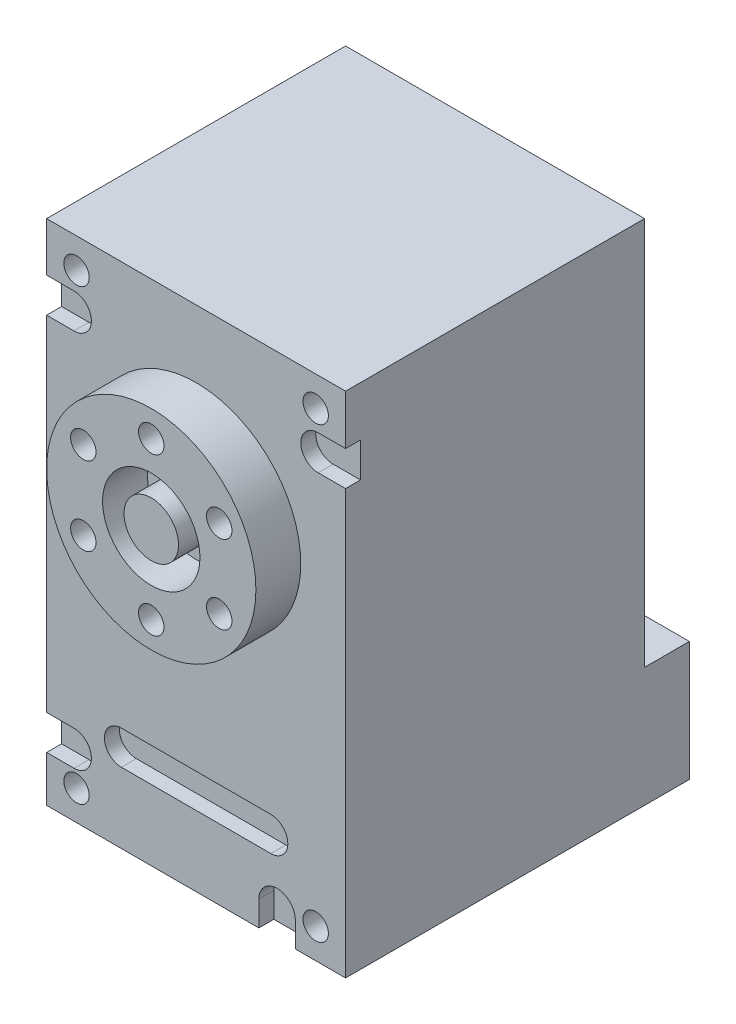
SolidWorks part; units mm, degrees
ref_plane "前视基准面" through (0, 0, 0) normal (0, 0, 1) x (1, 0, 0)
ref_plane "上视基准面" through (0, 0, 0) normal (0, 1, 0) x (1, 0, 0)
ref_plane "右视基准面" through (0, 0, 0) normal (1, 0, 0) x (0, 0, -1)
other "Configuration Table"
sketch "草图1" plane through (0, 0, 0) normal (0, 0, 1) x (1, 0, 0)
  line L0 (0, 0) -> (20, 0)
  line L1 (20, 0) -> (20, 34)
  line L2 (20, 34) -> (0, 34)
  line L3 (0, 34) -> (0, 0)
  line L4 (10, 0) -> (10, 34) construction
  line L5 (0, 17) -> (20, 17) construction
  circle A0 centre (2, 32) radius 0.85
  circle A1 centre (18, 32) radius 0.85
  circle A2 centre (18, 2) radius 0.85
  circle A3 centre (2, 2) radius 0.85
  circle A4 centre (10, 22.5) radius 7
  circle A5 centre (10, 27.75) radius 0.8504
  circle A6 centre (14.5466, 25.125) radius 0.8504
  circle A7 centre (14.5466, 19.875) radius 0.8504
  circle A8 centre (10, 17.25) radius 0.8504
  circle A9 centre (5.4534, 19.875) radius 0.8504
  circle A10 centre (5.4534, 25.125) radius 0.8504
  circle A11 centre (10, 22.5) radius 5.25
  circle A12 centre (10, 22.5) radius 3.2575
  circle A13 centre (10, 22.5) radius 1.8232
  point P34 (10, 22.5)
  dimension "D3" = 1.7
  dimension "D7" = 6
  dimension "D8" = 14
  dimension "D9" = 10.5
  dimension "D1" = 20
  dimension "D2" = 34
  dimension "D4" = 16
  dimension "D5" = 30
  dimension "D6" = 9.5
extrude "凸台-拉伸4" add sketch "草图1" along normal blind 3 contours A4 A11 A6 A7 A8 A9 A10 A5 | A6 A11 A5 A10 A9 A8 A7 A12 | A13 region at (3.198, 22.5, 0) region at (10, 26.7521, 0) region at (10, 22.5, 0)
sketch "草图3" plane through (0, 0, 3) normal (0, 0, 1) x (1, 0, 0)
extrude "凸台-拉伸5" add sketch "草图1<9>" against normal blind 20 contours A11 A7 | A7 A11 | A11 A5 | A11 A10 | A10 A11 | A11 A9 | A9 A11 | A11 A8 | A8 A11 | A6 A11 A5 A10 A9 A8 A7 A12 | A12 A13 | A13 | A1 | A0 | A2 | A3 | L2 L3 L0 L1 A4 A1 A0 A2 A3 | A4 A11 A6 A7 A8 A9 A10 A5 | A5 A11 | A6 region at (10, 15.3623, 0) region at (2, 32, 0) region at (18, 32, 0) region at (18, 2, 0) region at (2, 2, 0) region at (3.198, 22.5, 0) region at (10, 28.0982, 0) region at (10, 27.377, 0) region at (10, 26.7521, 0) region at (5.1518, 25.2991, 0) region at (5.7764, 24.9385, 0) region at (5.1518, 19.7009, 0) region at (5.7764, 20.0615, 0) region at (14.2236, 20.0615, 0) region at (14.8482, 19.7009, 0) region at (10, 16.9018, 0) region at (10, 17.623, 0) region at (6.8346, 22.5, 0) region at (10, 22.5, 0)
sketch "草图1<9>" plane through (0, 0, 0) normal (0, 0, 1) x (1, 0, 0) same geometry as "草图1"
sketch "草图4" plane through (0, 0, 0) normal (0, 0, 1) x (1, 0, 0)
sketch "草图6" plane through (0, 0, 0) normal (0, 0, 1) x (1, 0, 0)
sketch "草图7" plane through (0, 0, 0) normal (0, 0, 1) x (1, 0, 0)
  line L0 (10, 0) -> (10, 35.4001) construction
  line L1 (20, 0) -> (20, 34) construction
  line L2 (0, 17) -> (20, 17) construction
  line L3 (0, 0) -> (20, 0) construction
  circle A0 centre (2, 32) radius 0.85
  circle A3 centre (18, 32) radius 0.85
  circle A4 centre (18, 2) radius 0.85
  circle A5 centre (2, 2) radius 0.85
  dimension "D3" = 10
  dimension "D1" = 16
  dimension "D2" = 30
  dimension "D4" = 17
extrude "切除-拉伸1" cut sketch "草图7" against normal blind 1.5 contours A0 | A5 | A3 | A4
sketch "草图8" plane through (0, 0, 0) normal (-1, 0, 0) x (0, 0, 1)
  line L0 (-20, 0) -> (-23, 0)
  line L1 (-23, 0) -> (-23, 8)
  line L2 (-23, 8) -> (-20, 16)
  line L3 (-20, 34) -> (-20, 0) construction
  line L4 (-20, 16) -> (-20, 0)
  line L5 (-20, 34) -> (0, 34) construction
  line L6 (-20, 16) -> (-16, 16)
  line L7 (-16, 16) -> (-16, 8)
  line L8 (-16, 8) -> (-20, 8)
  line L9 (-23, 8) -> (-20, 8)
  point P10 (0, 0)
  point P13 (0, 0)
  dimension "D1" = 3
  dimension "D2" = 18
  dimension "D3" = 4
  dimension "D4" = 8
extrude "凸台-拉伸6" add sketch "草图8" against normal blind 20 contours L9 L1 L0 L4 region at (0, 4, -21.5)
sketch "草图9" plane through (0, 0, -20) normal (0, 0, -1) x (-1, 0, 0)
  line L0 (-10, 8) -> (-10, 13.8742) construction
  line L2 (0, 34) -> (0, 8) construction
  dimension "D1" = 10
sketch "草图11" plane through (0, 0, 0) normal (-1, 0, 0) x (0, 0, 1)
  line L0 (-23, 8) -> (-20, 15)
  line L1 (-20, -199992) -> (-20, 200013.8742) construction
  line L2 (-20, 15) -> (-20, 8)
  line L3 (-20, 8) -> (-23, 8)
  dimension "D1" = 7
extrude "凸台-拉伸7" add sketch "草图11" against normal blind 20
sketch "草图12" plane through (0, 0, 0) normal (-1, 0, 0) x (0, 0, 1)
  line L0 (-23, 8) -> (-20, 8)
  line L1 (-20, -199992) -> (-20, 200013.8742) construction
  line L2 (-20, 8) -> (-20, 15)
  line L3 (-20, 15) -> (-23, 8)
extrude "切除-拉伸2" cut sketch "草图12" against normal blind 4.5
sketch "草图13" plane through (20, 0, 0) normal (1, 0, 0) x (0, 0, -1)
  line L0 (23, 8) -> (20, 8)
  line L1 (20, -199992) -> (20, 200013.8742) construction
  line L2 (20, 8) -> (20, 15)
  line L3 (20, 15) -> (23, 8)
extrude "切除-拉伸3" cut sketch "草图13" against normal blind 4.5 contours L3 L0 L2
sketch "草图14" plane through (0, 0, -20) normal (0, 0, -1) x (-1, 0, 0)
  line L0 (-20, 0) -> (0, 0)
  line L1 (0, 0) -> (0, 34)
  line L2 (0, 34) -> (-20, 34)
  line L3 (-20, 34) -> (-20, 0)
  line L4 (-10, 0) -> (-10, 34) construction
  line L5 (-20, 17) -> (0, 17) construction
  circle A0 centre (-18, 32) radius 0.85
  circle A1 centre (-2, 32) radius 0.85
  circle A2 centre (-2, 2) radius 0.85
  circle A3 centre (-18, 2) radius 0.85
  circle A4 centre (-10, 22.5) radius 7
  circle A5 centre (-10, 27.75) radius 0.8504
  circle A11 centre (-10, 22.5) radius 5.25
  circle A12 centre (-10, 22.5) radius 3.2575
  circle A13 centre (-10, 22.5) radius 1.8232
  circle A14 centre (-5.4534, 25.125) radius 0.8504
  circle A15 centre (-5.4534, 19.875) radius 0.8504
  circle A16 centre (-10, 17.25) radius 0.8504
  circle A17 centre (-14.5466, 19.875) radius 0.8504
  circle A18 centre (-14.5466, 25.125) radius 0.8504
  point P32 (-10, 22.5)
  point P38 (-10, 22.5)
  dimension "D2" = 1.7
  dimension "D5" = 14
  dimension "D6" = 10.5
  dimension "D1" = 34
  dimension "D3" = 30
  dimension "D4" = 9.5
  dimension "D7" = 6
extrude "凸台-拉伸8" add sketch "草图14" along normal blind 3 contours A4 A11 A18 A5 A14 A15 A16 A17 | A11 A18 A17 A16 A15 A14 A5 A12 | A13 region at (16.802, 22.5, -20) region at (10, 26.7521, -20) region at (10, 22.5, -20)
sketch "草图15" plane through (0, 0, 0) normal (0, 0, 1) x (1, 0, 0)
  line L0 (0, 4.2275) -> (1.8335, 4.2275) construction
  line L4 (15.4187, -0.3137) -> (15.4187, 1.681) construction
  line L5 (14.1999, -0.3137) -> (14.1999, 1.681)
  line L6 (16.6374, -0.3137) -> (16.6374, 1.681)
  line L7 (0, 34) -> (0, 0) construction
  line L8 (0, 5.3867) -> (1.8335, 5.3867)
  line L9 (0, 3.0682) -> (1.8335, 3.0682)
  line L10 (-0.0011, 29.5642) -> (1.8324, 29.5642) construction
  line L11 (-0.0011, 30.7235) -> (1.8324, 30.7235)
  line L12 (-0.0011, 28.405) -> (1.8324, 28.405)
  line L13 (18.1621, 29.5159) -> (19.9956, 29.5159) construction
  line L14 (18.1621, 30.6752) -> (19.9956, 30.6752)
  line L15 (18.1621, 28.3567) -> (19.9956, 28.3567)
  line L16 (5, 5.8457) -> (15, 5.8457) construction
  line L17 (5, 6.9809) -> (15, 6.9809)
  line L18 (5, 4.7105) -> (15, 4.7105)
  line L19 (10, -199992) -> (10, 200013.8742) construction
  arc A2 (14.1999, -0.3137) -> (16.6374, -0.3137) centre (15.4187, -0.3137) ccw
  arc A3 (16.6374, 1.681) -> (14.1999, 1.681) centre (15.4187, 1.681) ccw
  arc A4 (0, 5.3867) -> (0, 3.0682) centre (0, 4.2275) ccw
  arc A5 (1.8335, 3.0682) -> (1.8335, 5.3867) centre (1.8335, 4.2275) ccw
  arc A6 (-0.0011, 30.7235) -> (-0.0011, 28.405) centre (-0.0011, 29.5642) ccw
  arc A7 (1.8324, 28.405) -> (1.8324, 30.7235) centre (1.8324, 29.5642) ccw
  arc A8 (18.1621, 30.6752) -> (18.1621, 28.3567) centre (18.1621, 29.5159) ccw
  arc A9 (19.9956, 28.3567) -> (19.9956, 30.6752) centre (19.9956, 29.5159) ccw
  arc A10 (5, 6.9809) -> (5, 4.7105) centre (5, 5.8457) ccw
  arc A11 (15, 4.7105) -> (15, 6.9809) centre (15, 5.8457) ccw
  point P4 (0.9167, 4.2275)
  point P11 (10, 5.8457)
  point P14 (15.4187, 0.6837)
  point P23 (0.9157, 29.5642)
  point P30 (19.0789, 29.5159)
  point P39 (0, 0)
  dimension "D1" = 5
  dimension "D2" = 5
extrude "切除-拉伸4" cut sketch "草图15" against normal blind 1 contours L11 A7 L12 A6 | L14 A9 L15 A8 | L18 A11 L17 A10 | L5 A3 L6 A2 | L9 A5 L8 A4
sketch "草图16" plane through (0, 0, -1) normal (0, 0, 1) x (1, 0, 0)
  circle A0 centre (15.4271, 1.685) radius 1
  circle A1 centre (1.8311, 4.1874) radius 0.9947
  circle A2 centre (1.8324, 29.5642) radius 1
  circle A3 centre (18.1621, 29.5159) radius 0.988
  point P2 (15.3927, 1.7309)
  point P3 (15.4271, 1.685)
  point P4 (1.8423, 4.1098)
  point P5 (1.8311, 4.1874)
  point P10 (2.5228, 9.5113)
  point P11 (1.8324, 29.5642)
  point P15 (18.1621, 29.5159)
  dimension "D1" = 2
